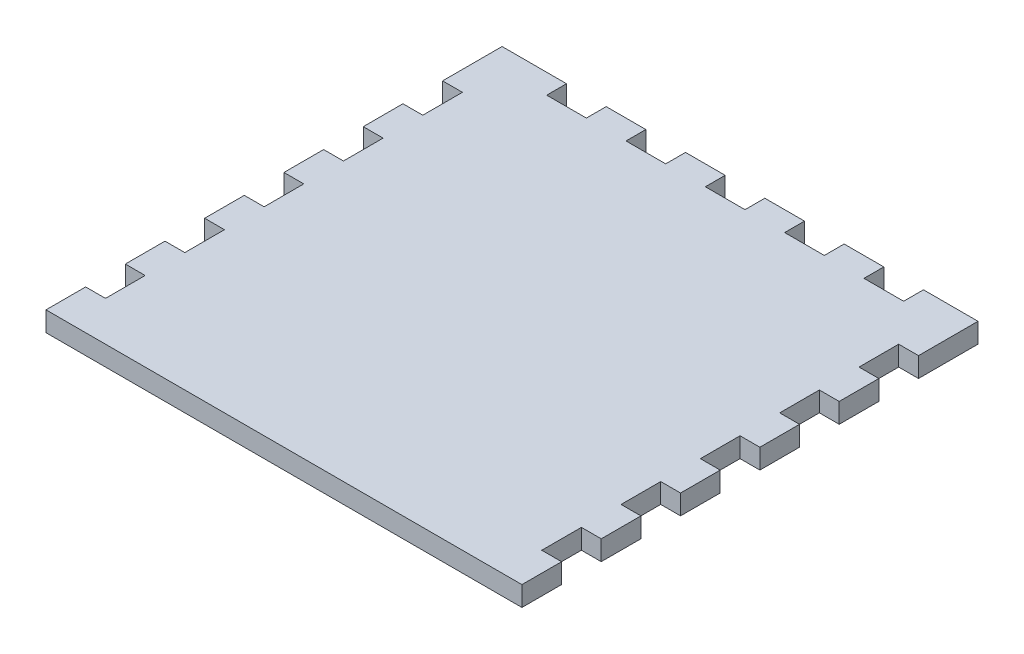
SolidWorks part; units mm, degrees
ref_plane "Front Plane" through (0, 0, 0) normal (0, 0, 1) x (1, 0, 0)
ref_plane "Top Plane" through (0, 0, 0) normal (0, 1, 0) x (1, 0, 0)
ref_plane "Right Plane" through (0, 0, 0) normal (1, 0, 0) x (0, 0, -1)
sketch "Sketch1" plane through (0, 0, 0) normal (0, 1, 0) x (1, 0, 0)
  line L1 (-139.7, -139.7) -> (139.7, -139.7)
  line L2 (-139.7, -139.7) -> (-139.7, 139.7)
  line L3 (-139.7, 139.7) -> (139.7, 139.7)
  line L4 (139.7, -139.7) -> (139.7, 139.7)
  line L5 (-139.7, -139.7) -> (139.7, 139.7) construction
  line L6 (-139.7, 139.7) -> (139.7, -139.7) construction
  point P0 (0, 0)
  dimension "D1" = 279.4
  dimension "D2" = 279.4
extrude "Boss-Extrude1" add sketch "Sketch1" along normal blind 12.7
sketch "Sketch2" plane through (139.7, 0, 0) normal (1, 0, 0) x (0, 0, -1)
  line L0 (-139.7, 12.7) -> (139.7, 12.7) construction
  line L1 (-139.7, 0) -> (-114.3, 0)
  line L2 (-139.7, 0) -> (-139.7, 12.7)
  line L3 (-139.7, 12.7) -> (-114.3, 12.7)
  line L4 (-114.3, 0) -> (-114.3, 12.7)
  dimension "D1" = 25.4
extrude "Boss-Extrude2" add sketch "Sketch2" along normal blind 12.7
pattern_linear "LPattern1" count 6 spacing 50.8 along (0, 0, -1) of "Boss-Extrude2"
mirror "Mirror1" about plane through (0, 0, 0) normal (1, 0, 0) of "LPattern1"
sketch "Sketch3" plane through (0, 0, -139.7) normal (0, 0, -1) x (-1, 0, 0)
  line L0 (-152.4, 12.7) -> (152.4, 12.7) construction
  line L1 (-142.875, 12.7) -> (-117.475, 12.7)
  line L2 (-142.875, 12.7) -> (-142.875, 0)
  line L3 (-142.875, 0) -> (-117.475, 0)
  line L4 (-117.475, 12.7) -> (-117.475, 0)
  line L5 (-152.4, 0) -> (152.4, 0) construction
  line L6 (-152.4, 0) -> (-152.4, 12.7) construction
  dimension "D1" = 9.525
  dimension "D2" = 25.4
extrude "Boss-Extrude3" add sketch "Sketch3" along normal blind 12.7
pattern_linear "LPattern2" count 6 spacing 50.8 along (-1, 0, 0) of "Boss-Extrude3"
sketch "Sketch5" plane through (0, 0, -139.7) normal (0, 0, -1) x (-1, 0, 0)
  line L11 (160.655, 0) -> (-160.655, 0) construction
  line L12 (-152.4, 12.7) -> (-127, 12.7)
  line L13 (-152.4, 12.7) -> (-152.4, 0)
  line L14 (-152.4, 0) -> (-127, 0)
  line L15 (-127, 12.7) -> (-127, 0)
  dimension "D1" = 25.4
extrude "Boss-Extrude4" add sketch "Sketch5" along normal blind 12.7
mirror "Mirror2" about plane through (0, 0, 0) normal (1, 0, 0) of "Boss-Extrude4"
